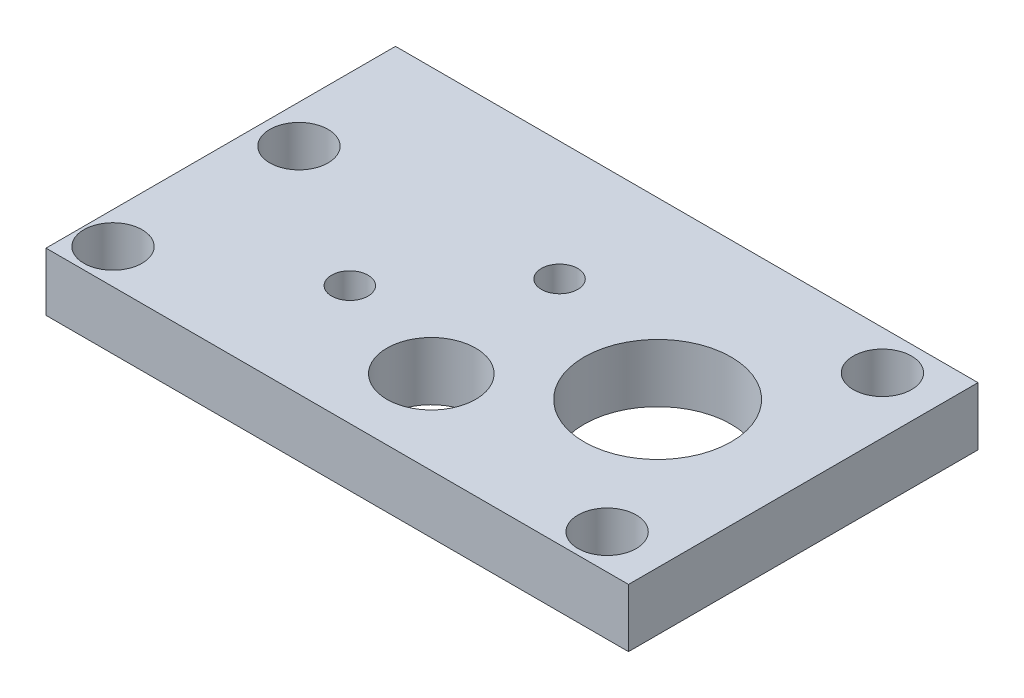
SolidWorks part; units mm, degrees
ref_plane "前视基准面" through (0, 0, 0) normal (0, 0, 1) x (1, 0, 0)
ref_plane "上视基准面" through (0, 0, 0) normal (0, 1, 0) x (1, 0, 0)
ref_plane "右视基准面" through (0, 0, 0) normal (1, 0, 0) x (0, 0, -1)
other "Configuration Table"
sketch "草图1" plane through (0, 0, 0) normal (0, 1, 0) x (1, 0, 0)
  line L1 (0, 0) -> (20, 0)
  line L2 (0, 0) -> (0, -12)
  line L3 (0, -12) -> (20, -12)
  line L4 (20, 0) -> (20, -12)
  circle A2 centre (9.7329, -4.1) radius 0.625
  circle A3 centre (10.3501, -9.1206) radius 1.525
  circle A4 centre (6.3314, -7.9) radius 0.625
  circle A5 centre (15, -6) radius 2.525
  point P5 (5, -6)
  dimension "D4" = 1.25
  dimension "D6" = 3.05
  dimension "D8" = 5.6
  dimension "D11" = 5.05
  dimension "D1" = 6
  dimension "D2" = 5
  dimension "D3" = 5.1
  dimension "D5" = 5.1
  dimension "D7" = 4.1
  dimension "D9" = 4.2
  dimension "D10" = 10
  dimension "D12" = 12
  dimension "D13" = 4.1
  dimension "D14" = 20
extrude "凸台-拉伸1" add sketch "草图1" along normal blind 2 contours L4 L3 L2 L1 | A2 | A3 | A4 | A5
sketch "草图3" plane through (0, 2, 0) normal (0, 1, 0) x (1, 0, 0)
  circle A0 centre (1.3106, -4.6263) radius 1
  circle A1 centre (1.1013, -10.8015) radius 1
  circle A2 centre (18.0672, -1.3489) radius 1
  circle A3 centre (18.0672, -10.8015) radius 1
  circle A4 centre (1.1013, -10.8015) radius 0.7
  circle A5 centre (1.3106, -4.6263) radius 0.7
  circle A6 centre (18.0672, -1.3489) radius 0.7
  circle A7 centre (18.0672, -10.8015) radius 0.7
  point P12 (0, 0)
  point P13 (0, 0)
  point P14 (0, 0)
  point P15 (0, 0)
  point P16 (0, 0)
  point P17 (0, 0)
  point P19 (0, 0)
  point P21 (0, 0)
  point P22 (0, 0)
  point P23 (0, 0)
  dimension "D1" = 1.4
  dimension "D2" = 2
extrude "切除-拉伸1" cut sketch "草图3" against normal through all contours A5 | A4 | A6 | A7
extrude "切除-拉伸2" cut sketch "草图3<3>" against normal blind 1.5 contours A0 | A1 | A3 | A2
sketch "草图3<3>" plane through (0, 2, 0) normal (0, 1, 0) x (1, 0, 0) same geometry as "草图3"
